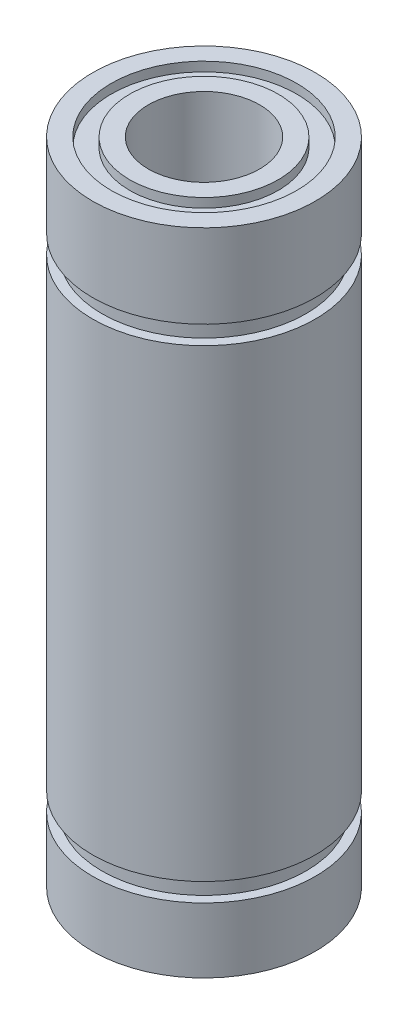
SolidWorks part; units mm, degrees
ref_plane "前基準面" through (0, 0, 0) normal (0, 0, 1) x (1, 0, 0)
ref_plane "上基準面" through (0, 0, 0) normal (0, 1, 0) x (1, 0, 0)
ref_plane "右基準面" through (0, 0, 0) normal (1, 0, 0) x (0, 0, -1)
sketch "草圖1" plane through (0, 0, 0) normal (0, 1, 0) x (1, 0, 0)
  circle A0 centre (0, 0) radius 3000
  circle A1 centre (0, 0) radius 6000
  circle A2 centre (0, 0) radius 5000
  circle A3 centre (0, 0) radius 4000
  dimension "D1" = 6000
  dimension "D2" = 10000
  dimension "D3" = 12000
  dimension "D4" = 8000
extrude "填料-伸長1" add sketch "草圖1" along normal mid plane 35000 contours A1 A2 region at (-5830.2944, 0, 0)
extrude "填料-伸長3" add sketch "草圖1<5>" along normal mid plane 35000 separate body contours A3 A0 region at (-3886.8629, 0, 0)
sketch "草圖1<5>" plane through (0, 0, 0) normal (0, 1, 0) x (1, 0, 0) same geometry as "草圖1"
extrude "填料-伸長4" add sketch "草圖1<6>" along normal mid plane 34000 contours A2 A3 region at (-4858.5786, 0, 0)
sketch "草圖1<6>" plane through (0, 0, 0) normal (0, 1, 0) x (1, 0, 0) same geometry as "草圖1"
ref_plane "平面1" through (0, 13000, 0) normal (0, 1, 0) x (1, 0, 0)
ref_plane "平面2" through (0, -13000, 0) normal (0, 1, 0) x (1, 0, 0)
sketch "草圖5" plane through (0, 13000, 0) normal (0, 1, 0) x (1, 0, 0)
  circle A0 centre (0, 0) radius 6000
  circle A1 centre (0, 0) radius 5500
  dimension "D1" = 11000
extrude "除料-伸長4" cut sketch "草圖5" against normal blind 1000
sketch "草圖6" plane through (0, -13000, 0) normal (0, 1, 0) x (1, 0, 0)
  circle A0 centre (0, 0) radius 6000
  circle A1 centre (0, 0) radius 5500
  dimension "D1" = 11000
extrude "除料-伸長5" cut sketch "草圖6" against normal blind 1000
